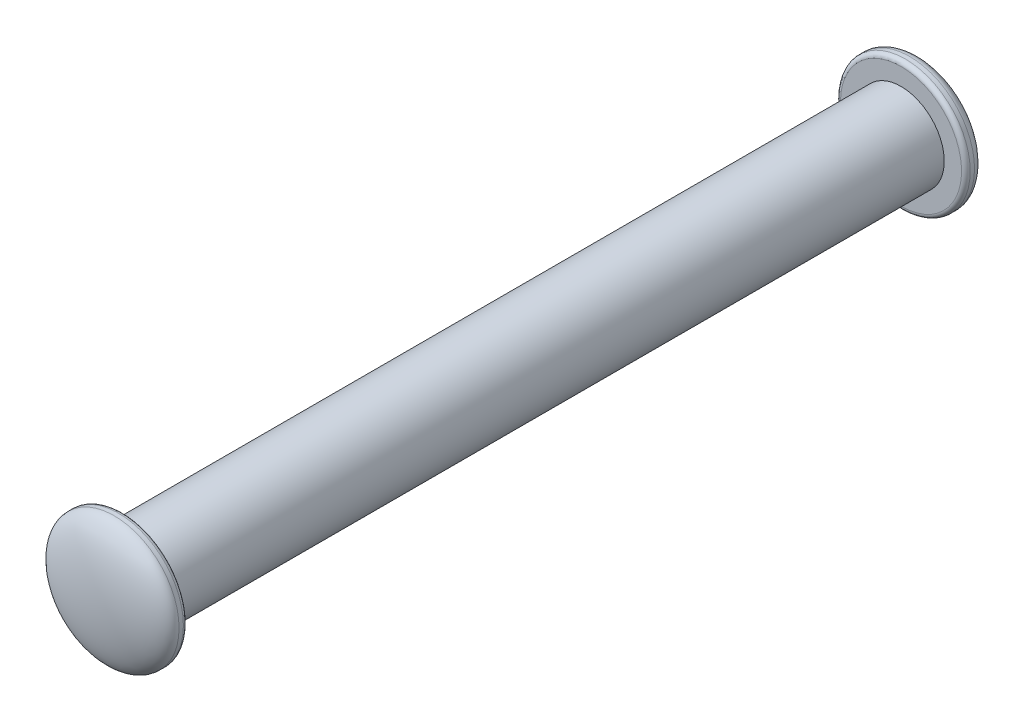
SolidWorks part; units mm, degrees
ref_plane "Front Plane" through (0, 0, 0) normal (0, 0, 1) x (1, 0, 0)
ref_plane "Top Plane" through (0, 0, 0) normal (0, 1, 0) x (1, 0, 0)
ref_plane "Right Plane" through (0, 0, 0) normal (1, 0, 0) x (0, 0, -1)
sketch "Sketch1" plane through (0, 0, 0) normal (0, 0, 1) x (1, 0, 0)
  circle A0 centre (0, 0) radius 0.5
  dimension "D1" = 1
extrude "Boss-Extrude1" add sketch "Sketch1" along normal mid plane 9
sketch "Sketch2" plane through (0, 0, 4.5) normal (0, 0, 1) x (1, 0, 0)
  circle A0 centre (0, 0) radius 0.75
  dimension "D1" = 1.5
extrude "Boss-Extrude2" add sketch "Sketch2" along normal blind 0.1
dome "Dome1" faces to dome 1 distance 0.25 reverse direction no elliptical dome yes face at (0.75, 0, 4.6) parameters "D1"=0.25
fillet "Fillet1" radius 0.05 1 edges at (0.75, 0, 4.5)
mirror "Mirror2" about plane through (0, 0, 0) normal (0, 0, 1) of "Boss-Extrude2", "Dome1", "Fillet1"
